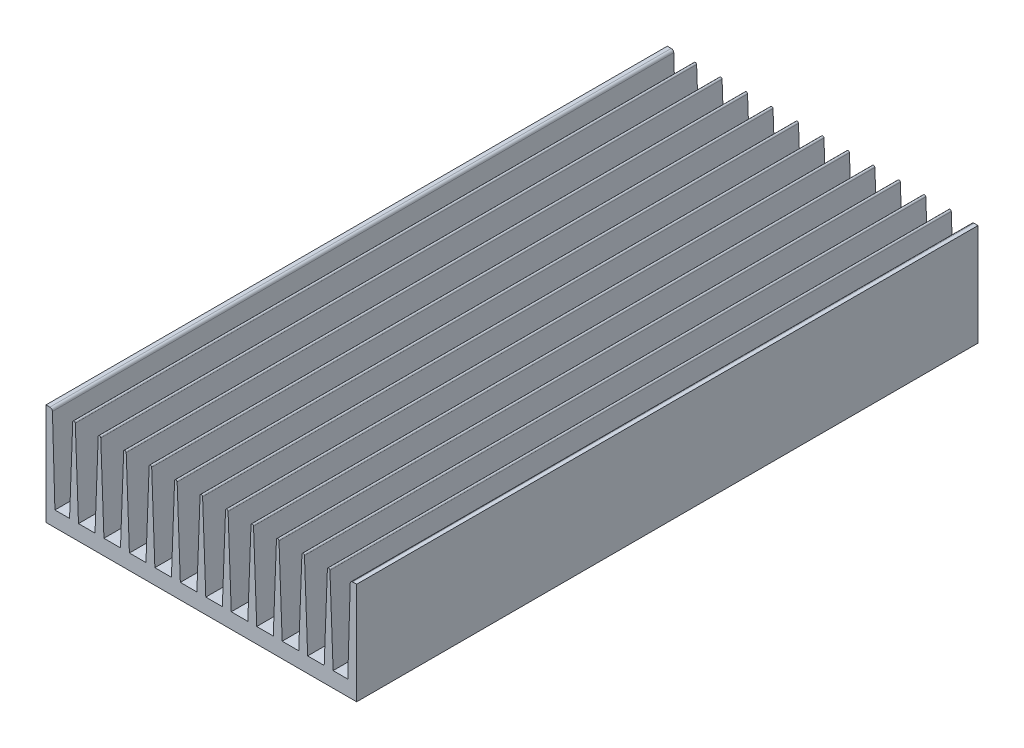
SolidWorks part; units mm, degrees
ref_plane "Спереди" through (0, 0, 0) normal (0, 0, 1) x (1, 0, 0)
ref_plane "Сверху" through (0, 0, 0) normal (0, 1, 0) x (1, 0, 0)
ref_plane "Справа" through (0, 0, 0) normal (1, 0, 0) x (0, 0, -1)
sketch "Эскиз1" plane through (0, 0, 0) normal (0, 0, 1) x (1, 0, 0)
  line L0 (0, 40) -> (1.529, 40)
  line L1 (0, 0) -> (122, 0)
  line L2 (2.5285, 39.0294) -> (3.5, 6)
  line L3 (0, 40) -> (0, 0)
  line L4 (122, 40) -> (122, 0)
  line L5 (61, 63.7127) -> (61, -22.2582) construction
  line L8 (122, 40) -> (120.471, 40)
  line L9 (119.4715, 39.0294) -> (118.5, 6)
  line L10 (3.5, 6) -> (118.5, 6)
  arc A0 (1.529, 40) -> (2.5285, 39.0294) centre (1.529, 39) cw
  arc A2 (120.471, 40) -> (119.4715, 39.0294) centre (120.471, 39) ccw
  point P18 (119.5, 40)
  dimension "D9" = 1
  dimension "D1" = 122
  dimension "D2" = 6
  dimension "D3" = 40
  dimension "D4" = 3.5
  dimension "D7" = 2.5
extrude "Вытянуть1" add sketch "Эскиз1" along normal blind 244
sketch "Эскиз2" plane through (0, 0, 244) normal (0, 0, 1) x (1, 0, 0)
  line L0 (118.5, 6) -> (3.5, 6) construction
  line L1 (10.5, 39.5) -> (9.25, 6)
  line L2 (11, 39.5) -> (11, 22.5548) construction
  line L3 (11.5, 39.5) -> (12.75, 6)
  line L4 (9.25, 6) -> (12.75, 6)
  line L6 (0, 40) -> (0, 0) construction
  arc A0 (10.5, 39.5) -> (11.5, 39.5) centre (11, 39.5) cw
  dimension "D1" = 34
  dimension "D3" = 0.5
  dimension "D2" = 3.5
  dimension "D4" = 11
  dimension "D5" = 1
extrude "Вытянуть3" add sketch "Эскиз2" against normal blind 244
pattern_curve "Кривая1" of "Вытянуть3" along edge at (61, 0, 0) parameters "D1"=11, "D3"=10, "D2"=1, "D4"=50
sketch "Эскиз3" plane through (0, 0, 0) normal (0, -1, 0) x (1, 0, 0)
  line L0 (-14.0506, 236) -> (137.5079, 236) construction
  line L1 (0, 244) -> (122, 244) construction
  line L2 (0, 244) -> (0, 0) construction
  line L3 (-46.7511, 122) -> (151.4312, 122) construction
  line L4 (0, 0) -> (122, 0) construction
  circle A0 centre (26, 236) radius 2.25
  circle A1 centre (96, 236) radius 2.25
  circle A2 centre (96, 8) radius 2.25
  circle A3 centre (26, 8) radius 2.25
  dimension "D2" = 70
  dimension "D4" = 4.5
  dimension "D1" = 8
  dimension "D3" = 26
extrude "Вырез-Вытянуть1" cut sketch "Эскиз3" against normal blind 6
sketch "Эскиз4" plane through (133.2401, 0, 310.1491) normal (0, -1, 0) x (-1, 0, 0)
  line L0 (71.2401, 227.1491) -> (71.2401, 87.5745) construction
  line L1 (133.2401, 66.1491) -> (133.2401, 310.1491) construction
  line L3 (25.2401, 237.1491) -> (91.2401, 237.1491) construction
  line L4 (25.2401, 237.1491) -> (25.2401, 285.1491) construction
  line L5 (25.2401, 285.1491) -> (91.2401, 285.1491) construction
  line L6 (91.2401, 237.1491) -> (91.2401, 285.1491) construction
  line L7 (133.2401, 310.1491) -> (11.2401, 310.1491) construction
  circle A0 centre (71.2401, 92.1491) radius 1.6
  circle A1 centre (71.2401, 227.1491) radius 1.6
  circle A2 centre (31.4901, 223.5491) radius 1.6
  circle A3 centre (31.4901, 139.7491) radius 1.6
  circle A4 centre (34.2401, 100.6491) radius 1.3
  circle A5 centre (91.2401, 285.1491) radius 1.6
  circle A6 centre (91.2401, 237.1491) radius 1.6
  circle A7 centre (25.2401, 237.1491) radius 1.6
  circle A8 centre (25.2401, 285.1491) radius 1.6
  dimension "D1" = 3.2
  dimension "D3" = 3.2
  dimension "D4" = 39.75
  dimension "D5" = 39.75
  dimension "D6" = 8.5
  dimension "D7" = 47.6
  dimension "D8" = 3.6
  dimension "D9" = 135
  dimension "D10" = 62
  dimension "D11" = 83
  dimension "D16" = 2.6
  dimension "D2" = 37
  dimension "D12" = 66
  dimension "D13" = 48
  dimension "D14" = 25
  dimension "D15" = 42
extrude "Вырез-Вытянуть2" cut sketch "Эскиз4" against normal blind 6
cosmetic thread "Условное изображение резьбы5" parameters "D2"=4
cosmetic thread "Условное изображение резьбы6" parameters "D2"=4
cosmetic thread "Условное изображение резьбы7" parameters "D2"=4
cosmetic thread "Условное изображение резьбы8" parameters "D2"=4
cosmetic thread "Условное изображение резьбы9" parameters "D2"=3
cosmetic thread "Условное изображение резьбы10" parameters "D2"=4
cosmetic thread "Условное изображение резьбы11" parameters "D2"=4
cosmetic thread "Условное изображение резьбы12" parameters "D2"=4
cosmetic thread "Условное изображение резьбы13" parameters "D2"=4
